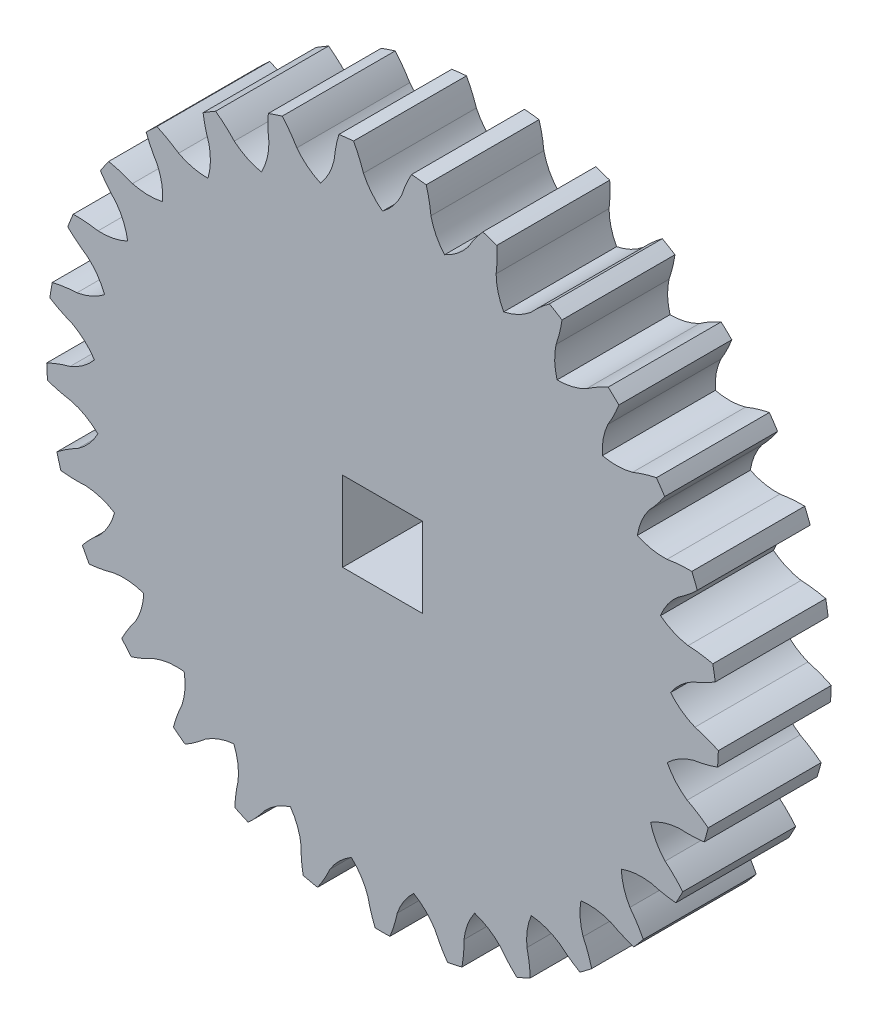
SolidWorks part; units mm, degrees
ref_plane "Front Plane" through (0, 0, 0) normal (0, 0, 1) x (1, 0, 0)
ref_plane "Top Plane" through (0, 0, 0) normal (0, 1, 0) x (1, 0, 0)
ref_plane "Right Plane" through (0, 0, 0) normal (1, 0, 0) x (0, 0, -1)
sketch "Sketch1" plane through (0, 0, 0) normal (0, 0, 1) x (1, 0, 0)
  line L1 (3.5355, -3.5355) -> (-3.5355, -3.5355)
  line L2 (3.5355, -3.5355) -> (3.5355, 3.5355)
  line L3 (3.5355, 3.5355) -> (-3.5355, 3.5355)
  line L4 (-3.5355, -3.5355) -> (-3.5355, 3.5355)
  line L5 (3.5355, -3.5355) -> (-3.5355, 3.5355) construction
  line L6 (3.5355, 3.5355) -> (-3.5355, -3.5355) construction
  circle A0 centre (0, 0) radius 29.75
  circle A1 centre (0, 0) radius 5 construction
  dimension "D1" = 59.5
  dimension "D2" = 10
extrude "Boss-Extrude1" add sketch "Sketch1" along normal blind 10
sketch "Sketch2" plane through (0, 0, 0) normal (0, 0, 1) x (1, 0, 0)
  line L0 (0, 0) -> (0, 36.6661) construction
  arc A25 (0, 25.5436) -> (-1.6909, 27.6123) centre (3.2409, 29.9179) cw
  arc A26 (-1.6909, 27.6123) -> (-6.9218, 34.1) centre (-12.7926, 24.0138) ccw
  arc A27 (-6.9218, 34.1) -> (0, 36.6661) centre (0.5436, 24.5815) cw
  arc A28 (6.9218, 34.1) -> (0, 36.6661) centre (-0.5436, 24.5815) ccw
  arc A29 (1.6909, 27.6123) -> (6.9218, 34.1) centre (12.7926, 24.0138) cw
  arc A30 (0, 25.5436) -> (1.6909, 27.6123) centre (-3.2409, 29.9179) ccw
  point P13 (-3.0185, 24.5815)
  point P14 (0, 23.5995)
  point P16 (-2.904, 26.4839)
  point P17 (0, 23.669)
  point P18 (-6.9845, 34.0505)
  point P19 (-1.6909, 27.6123)
extrude "Cut-Extrude1" cut sketch "Sketch2" along normal through all
pattern_circular "CirPattern1" count 29 over 360 about axis through (0, 0, 10) along (0, 0, -1) of "Cut-Extrude1"
sketch "Sketch3" plane through (0, 0, 0) normal (0, 0, 1) x (1, 0, 0)
  circle A0 centre (0, 0) radius 29.75
  dimension "D1" = 59.5
